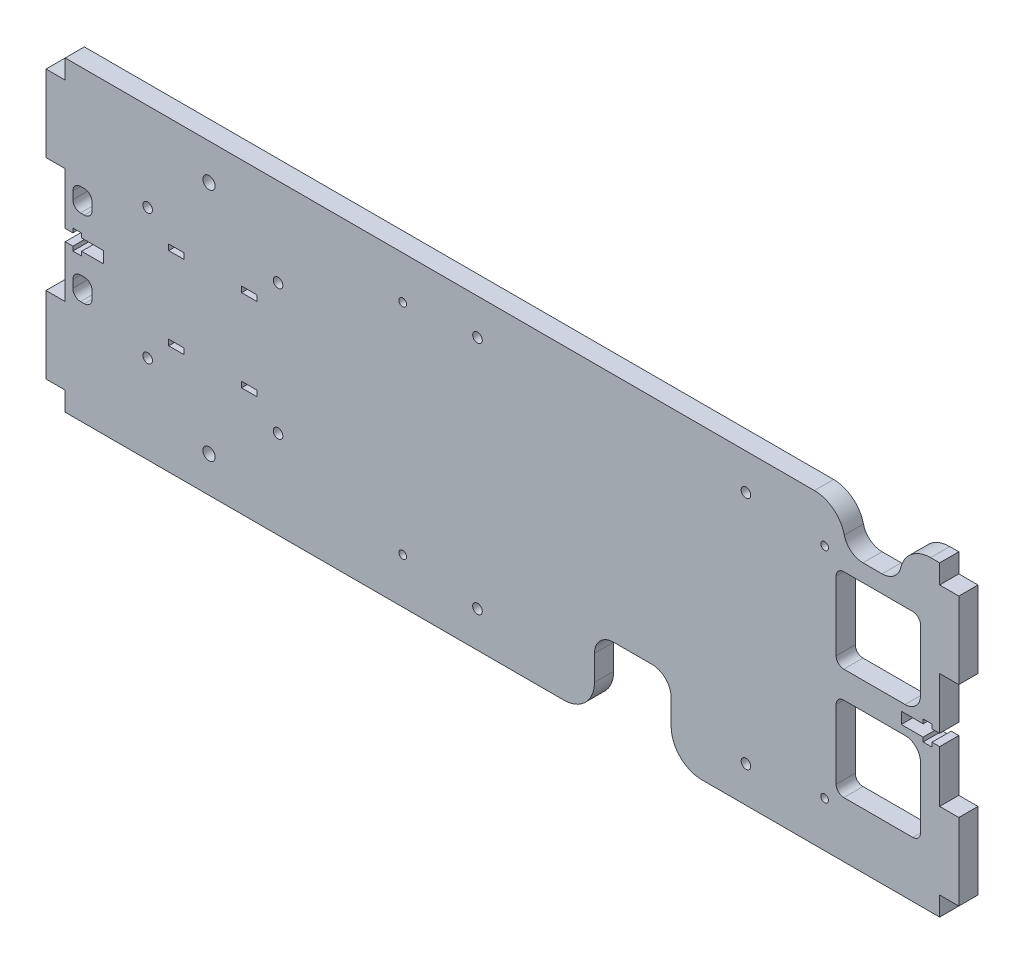
SolidWorks part; units mm, degrees
ref_plane "Plan de face" through (0, 0, 0) normal (0, 0, 1) x (1, 0, 0)
ref_plane "Plan de dessus" through (0, 0, 0) normal (0, 1, 0) x (1, 0, 0)
ref_plane "Plan de droite" through (0, 0, 0) normal (1, 0, 0) x (0, 0, -1)
sketch "Esquisse1" plane through (0, 0, 0) normal (0, 0, 1) x (1, 0, 0)
  line L0 (0, 35) -> (0, 15)
  line L1 (0, 15) -> (5, 15)
  line L2 (5, 15) -> (5, 1.5)
  line L3 (5, 1.5) -> (7, 1.5)
  line L4 (7, 1.5) -> (7, 2.6)
  line L5 (7, 2.6) -> (9.3, 2.6)
  line L6 (9.3, 2.6) -> (9.3, 1.5)
  line L7 (9.3, 1.5) -> (15, 1.5)
  line L8 (15, 1.5) -> (15, -1.5)
  line L9 (15, -1.5) -> (9.3, -1.5)
  line L10 (9.3, -1.5) -> (9.3, -2.6)
  line L11 (9.3, -2.6) -> (7, -2.6)
  line L12 (7, -2.6) -> (7, -1.5)
  line L13 (7, -1.5) -> (5, -1.5)
  line L14 (5, -1.5) -> (5, -15)
  line L15 (5, -15) -> (0, -15)
  line L16 (0, -15) -> (0, -35)
  line L17 (0, 35) -> (5, 35)
  line L18 (5, 35) -> (5, 40)
  line L19 (119, -36.5) -> (119, 67.7368) construction
  line L20 (0, 0) -> (119, 0) construction
  line L21 (238, 35) -> (238, 15)
  line L22 (238, 15) -> (233, 15)
  line L23 (233, 15) -> (233, 1.5)
  line L24 (233, 1.5) -> (231, 1.5)
  line L25 (231, 1.5) -> (231, 2.6)
  line L26 (231, 2.6) -> (228.7, 2.6)
  line L27 (228.7, 2.6) -> (228.7, 1.5)
  line L28 (228.7, 1.5) -> (223, 1.5)
  line L29 (223, 1.5) -> (223, -1.5)
  line L30 (223, -1.5) -> (228.7, -1.5)
  line L31 (228.7, -1.5) -> (228.7, -2.6)
  line L32 (228.7, -2.6) -> (231, -2.6)
  line L33 (231, -2.6) -> (231, -1.5)
  line L34 (231, -1.5) -> (233, -1.5)
  line L35 (233, -1.5) -> (233, -15)
  line L36 (233, -15) -> (238, -15)
  line L37 (238, -15) -> (238, -35)
  line L38 (5, 40) -> (233, 40)
  line L39 (233, 40) -> (233, 35)
  line L40 (233, 35) -> (238, 35)
  line L41 (238, -35) -> (233, -35)
  line L42 (233, -35) -> (233, -40)
  line L43 (233, -40) -> (5, -40)
  line L44 (5, -40) -> (5, -35)
  line L45 (5, -35) -> (0, -35)
  line L46 (32, -11.5) -> (32, -10)
  line L47 (32, 11.5) -> (36, 11.5)
  line L48 (32, 11.5) -> (32, 10)
  line L49 (32, 10) -> (36, 10)
  line L50 (36, 11.5) -> (36, 10)
  line L51 (51, 11.5) -> (55, 11.5)
  line L52 (51, 11.5) -> (51, 10)
  line L53 (51, 10) -> (55, 10)
  line L54 (55, 11.5) -> (55, 10)
  line L55 (32, -10) -> (36, -10)
  line L56 (36, -11.5) -> (36, -10)
  line L57 (32, -11.5) -> (36, -11.5)
  line L58 (51, -11.5) -> (51, -10)
  line L59 (51, -10) -> (55, -10)
  line L60 (55, -11.5) -> (55, -10)
  line L61 (51, -11.5) -> (55, -11.5)
  line L62 (239.1547, 0) -> (-3.4925, 0) construction
  line L63 (203, 28.8228) -> (93, 28.8228) construction
  line L64 (93, 28.8228) -> (93, -28.1772) construction
  line L65 (93, -28.1772) -> (203, -28.1772) construction
  line L66 (203, -28.1772) -> (203, 28.8228) construction
  line L67 (182.5, -30.615) -> (42.5, -30.615) construction
  line L68 (112.5, 30.615) -> (112.5, -30.615) construction
  circle A0 centre (203, -28.1772) radius 1
  circle A1 centre (203, 28.8228) radius 1
  circle A2 centre (93, -28.1772) radius 1
  circle A3 centre (93, 28.8228) radius 1
  circle A4 centre (112.5, -30.615) radius 1.25
  circle A5 centre (42.5, -30.615) radius 1.6
  circle A6 centre (182.5, -30.615) radius 1.25
  circle A7 centre (42.5, 30.615) radius 1.6
  circle A8 centre (182.5, 30.615) radius 1.25
  circle A9 centre (112.5, 30.615) radius 1.25
  point P31 (119, 33.5)
  dimension "D19" = 30
  dimension "D23" = 2.5
  dimension "D2" = 3
  dimension "D3" = 5.2
  dimension "D4" = 2.3
  dimension "D5" = 5
  dimension "D6" = 2
  dimension "D7" = 10
  dimension "D8" = 30
  dimension "D9" = 238
  dimension "D10" = 20
  dimension "D11" = 20
  dimension "D12" = 80
  dimension "D13" = 5
  dimension "D14" = 57
  dimension "D15" = 110
  dimension "D16" = 4
  dimension "D17" = 1.5
  dimension "D18" = 15
  dimension "D20" = 10
  dimension "D21" = 61.23
  dimension "D22" = 70
  dimension "D24" = 6.5
extrude "Boss.-Extru.1" add sketch "Esquisse1" along normal blind 5
sketch "Sketch1" plane through (0, 0, 0) normal (0, 0, -1) x (-1, 0, 0)
  line L0 (-5, 15) -> (-5, 1.5) construction
  line L5 (-5, -35) -> (-5, -40) construction
  line L6 (-233, 40) -> (-5, 40) construction
  line L7 (-208, 40) -> (-223, 40)
  line L8 (-208, 40) -> (-208, 30)
  line L9 (-208, 30) -> (-223, 30)
  line L10 (-223, 40) -> (-223, 30)
  line L11 (-12, 13) -> (-7, 13)
  line L12 (-236.561, 0) -> (-128.3605, 0) construction
  line L18 (-163, -40.4299) -> (-143, -40.4299)
  line L19 (-163, -40.4299) -> (-163, -20.4299)
  line L20 (-163, -20.4299) -> (-143, -20.4299)
  line L21 (-143, -40.4299) -> (-143, -20.4299)
  line L22 (-233, 35) -> (-233, 40) construction
  line L23 (-12, 13) -> (-12, 7)
  line L24 (-12, 7) -> (-7, 7)
  line L25 (-7, 13) -> (-7, 7)
  line L26 (-20.3235, 0) -> (4.719, 0) construction
  line L27 (-7, -13) -> (-7, -7)
  line L28 (-12, -7) -> (-7, -7)
  line L29 (-12, -13) -> (-12, -7)
  line L30 (-12, -13) -> (-7, -13)
  line L31 (-233, 40) -> (-5, 40) construction
  line L32 (-228, 25.5) -> (-206, 25.5)
  line L33 (-228, -25.5) -> (-206, -25.5)
  line L34 (-228, -25.5) -> (-228, -3.5)
  line L35 (-228, -3.5) -> (-206, -3.5)
  line L36 (-206, -25.5) -> (-206, -3.5)
  line L37 (-228, 25.5) -> (-228, 3.5)
  line L38 (-206, 25.5) -> (-206, 3.5)
  line L39 (-228, 3.5) -> (-206, 3.5)
  line L40 (-233, -15) -> (-233, -1.5) construction
  line L41 (-51, -10.75) -> (-36, -10.75) construction
  line L42 (-60.5, 17) -> (-26.5, 17) construction
  line L43 (-60.5, 17) -> (-60.5, -17) construction
  line L44 (-60.5, -17) -> (-26.5, -17) construction
  line L45 (-26.5, 17) -> (-26.5, -17) construction
  line L46 (-51, -10) -> (-51, -11.5) construction
  line L47 (-36, -11.5) -> (-36, -10) construction
  line L48 (-43.5, -14.432) -> (-43.5, 22.5) construction
  circle A0 centre (-60.5, 17) radius 1.25
  circle A1 centre (-60.5, -17) radius 1.25
  circle A3 centre (-26.5, 17) radius 1.25
  circle A4 centre (-26.5, -17) radius 1.25
  point P24 (-5, -37.5)
  point P46 (-26.5, 0)
  point P55 (-43.5, -10.75)
  point P56 (-43.5, -17)
  dimension "D1" = 10
  dimension "D2" = 15
  dimension "D3" = 20
  dimension "D4" = 22
  dimension "D5" = 22
  dimension "D6" = 3.5
  dimension "D7" = 10
  dimension "D8" = 138
  dimension "D9" = 20
  dimension "D10" = 6
  dimension "D11" = 5
  dimension "D12" = 2
  dimension "D13" = 27
  dimension "D14" = 5
  dimension "D15" = 34
  dimension "D16" = 34
extrude "Cut-Extrude1" cut sketch "Sketch1" against normal blind 10
fillet "Fillet2" radius 5 4 edges at (223, 30, 2.5) (208, 30, 2.5) (143, -20.4299, 2.5) (163, -20.4299, 2.5)
fillet "Fillet3" radius 2 6 edges at (228, -25.5, 2.5) (206, -3.5, 2.5) (206, -25.5, 2.5) (206, 3.5, 2.5) (228, 25.5, 2.5) (206, 25.5, 2.5)
fillet "Congé1" radius 8 4 edges at (223, 40, 2.5) (208, 40, 2.5) (163, -40, 2.5) (143, -40, 2.5)
fillet "Congé2" radius 2 8 edges at (7, -13, 2.5) (12, -13, 2.5) (7, -7, 2.5) (12, -7, 2.5) (12, 7, 2.5) (7, 7, 2.5) (7, 13, 2.5) (12, 13, 2.5)
fillet "Congé3" radius 4 2 edges at (228, 3.5, 2.5) (228, -3.5, 2.5)
